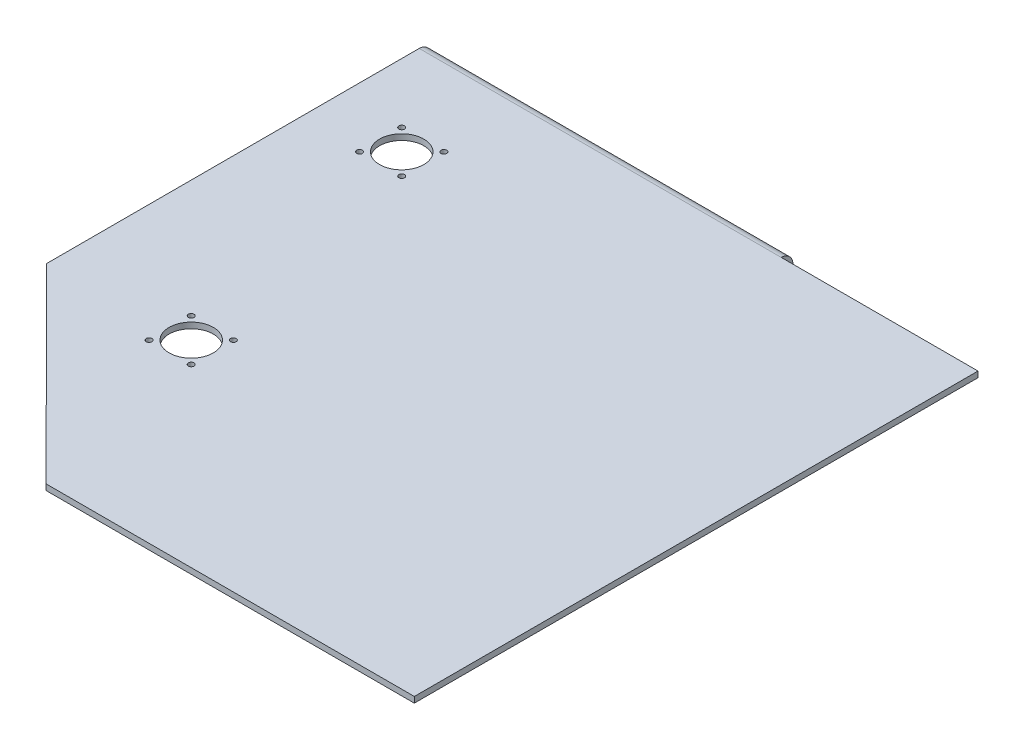
SolidWorks part; units mm, degrees
note: The reader was unsure of these and kept them because the rebuilt part matched: flange length of "Edge-Flange1".
material "6061-T6 (SS)"
ref_plane "X-Y Datum" through (0, 0, 0) normal (0, 0, 1) x (1, 0, 0)
ref_plane "X-Z Datum" through (0, 0, 0) normal (0, 1, 0) x (1, 0, 0)
ref_plane "Y-Z Datum" through (0, 0, 0) normal (1, 0, 0) x (0, 0, -1)
sketch "Sketch1" plane through (0, 0, 0) normal (0, 1, 0) x (1, 0, 0)
  line L1 (154.686, -16.51) -> (355.6, -16.51)
  line L2 (50.8, 87.757) -> (50.8, 290.957)
  line L3 (50.8, 290.957) -> (355.6, 290.957)
  line L4 (355.6, -16.51) -> (355.6, 290.957)
  line L6 (50.8, 87.757) -> (154.686, -16.51)
  line L7 (333.375, -16.51) -> (352.425, -16.51) construction
  dimension "D1" = 304.8
  dimension "D2" = 134.895
  dimension "D3" = 203.2
  dimension "D4" = 200.914
base flange "Base-Flange1" sketch "Sketch1" thickness 3.175 reverse thickness direction no parameters "D1"=3.175
edge flange "Edge-Flange1" sketch "Sketch8" flange angle 90 flange length 38.1 flange position bend outside bend radius 3.175 thickness 3.175 relief rectangular parameters "D6"=10
sketch "Sketch8" plane through (0, -3.175, -290.957) normal (0, 0, 1) x (-1, 0, 0)
  line L3 (-248.3129, 34.925) -> (-50.8, 34.925)
  line L4 (-50.8, 34.925) -> (-50.8, 0)
  line L5 (-50.8, 0) -> (-355.6, 0) construction
  line L10 (-50.8, 0) -> (-248.3129, 0)
  line L11 (-248.3129, 0) -> (-248.3129, 34.925)
bend "EdgeBend1" bend radius 3.175 bend angle 90 parameters "D5"=1
sketch "Sketch9" plane through (0, 0, 0) normal (0, 1, 0) x (1, 0, 0)
  line L6 (355.6, -16.51) -> (355.6, 290.957)
  line L7 (355.6, 290.957) -> (248.3129, 290.957)
  line L8 (248.3129, 290.957) -> (50.8, 290.957)
  line L9 (50.8, 290.957) -> (50.8, 87.757)
  line L10 (50.8, 87.757) -> (154.686, -16.51)
  line L11 (154.686, -16.51) -> (355.6, -16.51)
  line L12 (355.6, -16.51) -> (355.6, 290.957)
  line L13 (355.6, 290.957) -> (248.3129, 290.957)
  line L14 (248.3129, 290.957) -> (50.8, 290.957)
  line L15 (50.8, 290.957) -> (50.8, 87.757)
  line L16 (50.8, 87.757) -> (154.686, -16.51)
  line L17 (154.686, -16.51) -> (355.6, -16.51)
  arc A0 (84.925, 225.8332) -> (81.825, 225.8332) centre (83.375, 225.8332) ccw construction
  arc A1 (81.825, 225.8332) -> (84.925, 225.8332) centre (83.375, 225.8332) ccw construction
  arc A2 (104.825, 225.8332) -> (107.925, 225.8332) centre (106.375, 225.8332) ccw construction
  arc A3 (107.925, 225.8332) -> (104.825, 225.8332) centre (106.375, 225.8332) ccw construction
  arc A4 (104.825, 248.8332) -> (107.925, 248.8332) centre (106.375, 248.8332) ccw construction
  arc A5 (107.925, 248.8332) -> (104.825, 248.8332) centre (106.375, 248.8332) ccw construction
  arc A6 (84.925, 248.8332) -> (81.825, 248.8332) centre (83.375, 248.8332) ccw construction
  arc A7 (81.825, 248.8332) -> (84.925, 248.8332) centre (83.375, 248.8332) ccw construction
  arc A8 (113.37, 102.4662) -> (116.47, 102.4662) centre (114.92, 102.4662) ccw construction
  arc A9 (116.47, 102.4662) -> (113.37, 102.4662) centre (114.92, 102.4662) ccw construction
  arc A10 (136.37, 102.4662) -> (139.47, 102.4662) centre (137.92, 102.4662) ccw construction
  arc A11 (139.47, 102.4662) -> (136.37, 102.4662) centre (137.92, 102.4662) ccw construction
  arc A12 (136.37, 79.4662) -> (139.47, 79.4662) centre (137.92, 79.4662) ccw construction
  arc A13 (139.47, 79.4662) -> (136.37, 79.4662) centre (137.92, 79.4662) ccw construction
  arc A14 (113.37, 79.4662) -> (116.47, 79.4662) centre (114.92, 79.4662) ccw construction
  arc A15 (116.47, 79.4662) -> (113.37, 79.4662) centre (114.92, 79.4662) ccw construction
  arc A16 (84.925, 225.8332) -> (81.825, 225.8332) centre (83.375, 225.8332) ccw
  arc A17 (81.825, 225.8332) -> (84.925, 225.8332) centre (83.375, 225.8332) ccw
  arc A18 (104.825, 225.8332) -> (107.925, 225.8332) centre (106.375, 225.8332) ccw
  arc A19 (107.925, 225.8332) -> (104.825, 225.8332) centre (106.375, 225.8332) ccw
  arc A20 (104.825, 248.8332) -> (107.925, 248.8332) centre (106.375, 248.8332) ccw
  arc A21 (107.925, 248.8332) -> (104.825, 248.8332) centre (106.375, 248.8332) ccw
  arc A22 (84.925, 248.8332) -> (81.825, 248.8332) centre (83.375, 248.8332) ccw
  arc A23 (81.825, 248.8332) -> (84.925, 248.8332) centre (83.375, 248.8332) ccw
  arc A24 (113.37, 102.4662) -> (116.47, 102.4662) centre (114.92, 102.4662) ccw
  arc A25 (116.47, 102.4662) -> (113.37, 102.4662) centre (114.92, 102.4662) ccw
  arc A26 (136.37, 102.4662) -> (139.47, 102.4662) centre (137.92, 102.4662) ccw
  arc A27 (139.47, 102.4662) -> (136.37, 102.4662) centre (137.92, 102.4662) ccw
  arc A28 (136.37, 79.4662) -> (139.47, 79.4662) centre (137.92, 79.4662) ccw
  arc A29 (139.47, 79.4662) -> (136.37, 79.4662) centre (137.92, 79.4662) ccw
  arc A30 (113.37, 79.4662) -> (116.47, 79.4662) centre (114.92, 79.4662) ccw
  arc A31 (116.47, 79.4662) -> (113.37, 79.4662) centre (114.92, 79.4662) ccw
  circle A32 centre (94.875, 237.3332) radius 12.065
  circle A33 centre (126.42, 90.9662) radius 12.065
  dimension "D2" = 24.13
  dimension "D1" = 0
extrude "Cut-Extrude1" cut sketch "Sketch9" against normal blind 3.175 contours A16 A17 | A18 A19 | A20 A21 | A22 A23 | A32 | A28 A29 | A26 A27 | A33 | A24 A25 | A30 A31 normal cut yes
sketch "Bend-Lines1" [suppressed] plane through (0, 0, 0) normal (0, 1, 0) x (1, 0, 0)
sketch "Bounding-Box1" [suppressed] plane through (0, 0, 0) normal (0, 1, 0) x (1, 0, 0)
sheet metal parameters "Sheet-Metal1" thickness 3.175 parameters "D1"=3.175
flat pattern "Flat-Pattern1" [suppressed]
sketch "Bend-Lines2" plane through (0, 0, 0) normal (0, 1, 0) x (1, 0, 0)
sketch3d "Bounding-Box2" [suppressed]
  line L0 (0, 0, 0) -> (0, 290.83, 0) construction
  line L1 (-201.2086, 0, 0) -> (-201.2086, 290.83, 0) construction
  line L2 (0, 0, 0) -> (-201.2086, 0, 0) construction
  line L3 (0, 290.83, 0) -> (-201.2086, 290.83, 0) construction
sheet metal parameters "Sheet-Metal2" thickness 3.175 parameters "D1"=3.175
flat pattern "Flat-Pattern1"
sketch "Bend-Lines2" plane through (0, 0, 0) normal (0, 1, 0) x (1, 0, 0)
  line L0 (248.3129, 294.6975) -> (50.8, 294.6975) construction
  line L1 (248.3129, 294.6975) -> (50.8, 294.6975) construction
sketch3d "Bounding-Box2" [suppressed]
  line L0 (50.8, -16.51, 0) -> (50.8, 330.1879, 0) construction
  line L1 (355.6, -16.51, 0) -> (355.6, 330.1879, 0) construction
  line L2 (50.8, -16.51, 0) -> (355.6, -16.51, 0) construction
  line L3 (50.8, 330.1879, 0) -> (355.6, 330.1879, 0) construction
bend of the flat pattern "Flatten-<EdgeBend1>1"
sheet metal parameters "Sheet-Metal3" thickness 3.175 parameters "D1"=3.175
flat pattern "Flat-Pattern1"
sketch "Bend-Lines2" plane through (0, 0, 0) normal (0, 1, 0) x (1, 0, 0)
  line L0 (248.3129, 294.6975) -> (50.8, 294.6975) construction
  line L1 (248.3129, 294.6975) -> (50.8, 294.6975) construction
sketch3d "Bounding-Box2" [suppressed]
  line L0 (50.8, -16.51, 0) -> (50.8, 330.1879, 0) construction
  line L1 (355.6, -16.51, 0) -> (355.6, 330.1879, 0) construction
  line L2 (50.8, -16.51, 0) -> (355.6, -16.51, 0) construction
  line L3 (50.8, 330.1879, 0) -> (355.6, 330.1879, 0) construction
bend of the flat pattern "Flatten-<EdgeBend1>1"
